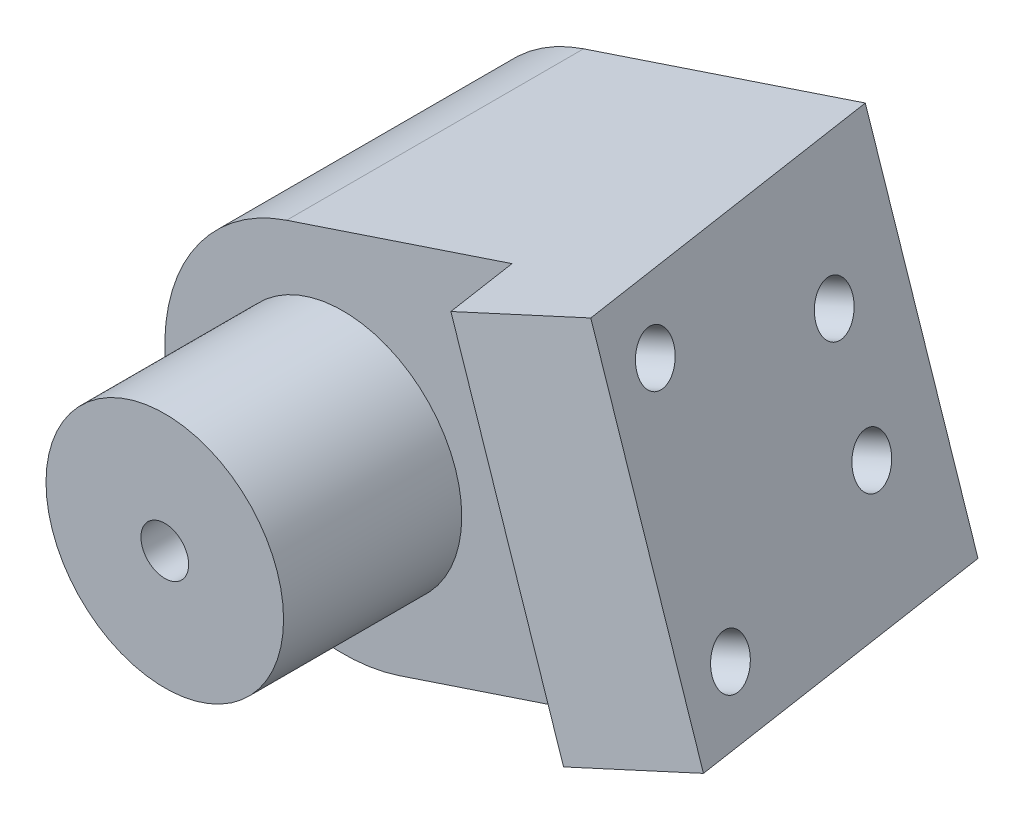
SolidWorks part; units mm, degrees
material "6061 Alloy"
ref_plane "Front Plane" through (0, 0, 0) normal (0, 0, 1) x (1, 0, 0)
ref_plane "Top Plane" through (0, 0, 0) normal (0, 1, 0) x (1, 0, 0)
ref_plane "Right Plane" through (0, 0, 0) normal (1, 0, 0) x (0, 0, -1)
sketch "Sketch1" plane through (0, 0, 0) normal (0, 0, 1) x (1, 0, 0)
  line L0 (0, 0) -> (228.6, 76.2) construction
  line L1 (18.0724, 26.1046) -> (30.1207, -10.0402)
  line L2 (18.0724, 26.1046) -> (-6.0241, 18.0724)
  line L3 (30.1207, -10.0402) -> (6.0241, -18.0724)
  arc A0 (-6.0241, 18.0724) -> (6.0241, -18.0724) centre (0, 0) ccw
  point P6 (24.0966, 8.0322)
  dimension "D1" = 38.1
  dimension "D2" = 76.2
  dimension "D3" = 228.6
  dimension "D4" = 25.4
  dimension "D5" = 38.1
extrude "Boss-Extrude1" add sketch "Sketch1" along normal blind 31.75
sketch "Sketch10" plane through (-6.0241, 18.0724, 0) normal (-0.3162, 0.9487, 0) x (0.9487, 0.3162, 0)
  line L0 (25.4, 0) -> (31.75, 0)
  line L1 (31.75, 0) -> (40.0158, -37.1926)
  line L2 (40.0158, -37.1926) -> (27.2406, -40.0318)
  line L3 (27.2406, -40.0318) -> (25.4, -31.75)
  line L4 (25.4, -31.75) -> (25.4, 0) construction
  line L5 (25.4, 0) -> (25.4, -31.75)
  dimension "D1" = 38.1
  dimension "D2" = 6.35
  dimension "D3" = 12.53
extrude "Boss-Extrude4" add sketch "Sketch10" against normal blind 38.1 contours L1 L2 L3 L5 L0
sketch "Sketch11" plane through (0, 0, 31.75) normal (0, 0, 1) x (1, 0, 0)
  circle A0 centre (0, 0) radius 12.7
  dimension "D1" = 25.4
extrude "Boss-Extrude5" add sketch "Sketch11" along normal blind 19.05
hole_wizard "1/4-20 Tapped Hole3" positions "Sketch13" profile "Sketch12" tap size "1/4-20" standard "ANSI Inch"
sketch "Sketch13" plane through (0, 0, 50.8) normal (0, 0, 1) x (1, 0, 0)
  point P0 (0, 0)
sketch "Sketch12" plane through (0, 0, 50.8) normal (1, 0, 0) x (0, -1, 0)
  line L0 (0, 0) -> (0, 39.6338)
  line L1 (0, 39.6338) -> (2.5527, 38.1)
  line L2 (2.5527, 38.1) -> (2.5527, 0)
  line L5 (2.5527, 0) -> (0, 0)
  line L10 (0, 39.6338) -> (-2.5527, 38.1) construction
  line L11 (0, -6.35) -> (0, 107.95) construction
  dimension "Tap Drill Dia." = 5.1054
  dimension "Tap Drill Depth" = 38.1
  dimension "Drill Angle" = 118
cosmetic thread "Hole Thread9" parameters "D1"=34.925, "D2"=6.35
hole_wizard "1/4-20 Tapped Hole4" positions "Sketch15" profile "Sketch14" tap size "1/4-20" standard "ANSI Inch"
sketch "Sketch15" plane through (28.703, 9.5677, -6.7241) normal (0.9261, 0.3087, -0.217) x (-0.2058, -0.0686, -0.9762)
  line L0 (-44.9882, -19.05) -> (-44.9882, 19.05) construction
  line L1 (-6.8882, 19.05) -> (-44.9882, 19.05) construction
  line L2 (-6.8882, -19.05) -> (-44.9882, -19.05) construction
  line L3 (-6.8882, -19.05) -> (-6.8882, 19.05) construction
  point P0 (-38.6382, 12.7)
  point P2 (-16.4132, 6.35)
  point P4 (-16.4132, -6.35)
  point P6 (-38.6382, -12.7)
  dimension "D1" = 6.35
  dimension "D2" = 6.35
  dimension "D3" = 6.35
  dimension "D4" = 12.7
  dimension "D5" = 12.7
  dimension "D6" = 9.525
sketch "Sketch14" plane through (32.6393, 24.2667, 30.9938) normal (-0.0699, 0.7054, 0.7054) x (-0.3708, 0.6381, -0.6748)
  line L0 (0, 0) -> (0, 14.2338)
  line L1 (0, 14.2338) -> (2.5527, 12.7)
  line L2 (2.5527, 12.7) -> (2.5527, 0)
  line L5 (2.5527, 0) -> (0, 0)
  line L10 (0, 14.2338) -> (-2.5527, 12.7) construction
  line L11 (0, -6.35) -> (0, 107.95) construction
  dimension "Tap Drill Dia." = 5.1054
  dimension "Tap Drill Depth" = 12.7
  dimension "Drill Angle" = 118
cosmetic thread "Hole Thread10" parameters "D1"=11.7093, "D2"=6.35
cosmetic thread "Hole Thread11" parameters "D1"=12.7, "D2"=6.35
cosmetic thread "Hole Thread12" parameters "D1"=12.7, "D2"=6.35
cosmetic thread "Hole Thread13" parameters "D1"=11.7093, "D2"=6.35
sketch "Sketch16" plane through (0, 0, 0) normal (0, 0, -1) x (-1, 0, 0)
  line L0 (0, 0) -> (-27.1086, 9.0362) construction
  line L1 (-30.5782, -6.541) -> (-16.9994, -3.995)
  line L2 (-31.8416, -5.1627) -> (-17.2919, -2.4347)
  line L4 (-22.0885, 24.0966) -> (0, 0) construction
  line L5 (0, 0) -> (-32.1287, -6.0241) construction
  line L6 (-22.3756, 23.2351) -> (-12.3728, 12.3229)
  line L7 (5.0201, 15.0603) -> (-22.0885, 24.0966)
  line L8 (-22.0885, 24.0966) -> (-32.1287, -6.0241)
  line L9 (-32.1287, -6.0241) -> (-5.0201, -15.0603)
  line L10 (-1.8814, 17.3609) -> (-20.538, 23.5797)
  line L11 (-22.3756, 23.2351) -> (-31.8416, -5.1627)
  line L12 (-30.5782, -6.541) -> (-11.9216, -12.7598)
  line L13 (-20.538, 23.5797) -> (-11.2025, 13.3956)
  line L14 (-14.6146, 17.1178) -> (-15.7848, 16.0451) construction
  arc A0 (-16.9994, -3.995) -> (-11.9216, -12.7598) centre (0, 0) ccw
  arc A1 (-12.3728, 12.3229) -> (-17.2919, -2.4347) centre (0, 0) ccw
  arc A3 (-5.0201, -15.0603) -> (5.0201, 15.0603) centre (0, 0) ccw
  arc A5 (-1.8814, 17.3609) -> (-11.2025, 13.3956) centre (0, 0) ccw
  point P14 (-15.1997, 16.5815)
  dimension "D2" = 17.4625
  dimension "D3" = 1.5875
  dimension "D1" = 3.175
extrude "Cut-Extrude3" cut sketch "Sketch16" against normal blind 3.175
sketch "Sketch17" plane through (0, 0, 0) normal (0, 0, -1) x (-1, 0, 0)
  circle A0 centre (0, 0) radius 15.875
  dimension "D1" = 31.75
extrude "Cut-Extrude4" cut sketch "Sketch17" against normal blind 15.875
fillet "Fillet3" radius 1.5875 10 edges at (1.8814, 17.3609, 1.5875) (11.2025, 13.3956, 1.5875) (20.538, 23.5797, 1.5875) (22.3756, 23.2351, 1.5875) (12.3728, 12.3229, 1.5875) (17.2919, -2.4347, 1.5875) (16.9994, -3.995, 1.5875) (11.9216, -12.7598, 1.5875) (31.8416, -5.1627, 1.5875) (30.5782, -6.541, 1.5875)
ref_axis "Axis1" through (0, 0, 15.875) along (0, 0, 1)
sketch "Sketch18" plane through (28.703, 9.5677, -6.7241) normal (0.9261, 0.3087, -0.217) x (-0.2058, -0.0686, -0.9762)
  line L0 (-6.8882, 19.05) -> (-44.9882, -19.05) construction
  line L1 (-44.9882, -19.05) -> (-44.9882, 19.05) construction
  line L2 (-6.8882, -19.05) -> (-44.9882, 19.05) construction
  point P9 (-25.9382, 0)
sketch "Sketch19" plane through (0, 0, 15.875) normal (0, 0, -1) x (-1, 0, 0)
  line L0 (0, 0) -> (0, 15.875) construction
  line L1 (1.5875, 4.4901) -> (1.5875, 15.7954)
  line L2 (-1.5875, 4.4901) -> (-1.5875, 15.7954)
  line L3 (-1.5875, 10.1428) -> (1.5875, 10.1428) construction
  line L4 (3.7798, 2.8973) -> (14.5318, 6.3909)
  line L5 (4.7609, -0.1223) -> (15.5129, 3.3713)
  line L6 (3.9235, -2.6995) -> (10.5686, -11.8457)
  line L7 (1.3549, -4.5657) -> (8, -13.7119)
  line L8 (-1.3549, -4.5657) -> (-8, -13.7119)
  line L9 (-3.9235, -2.6995) -> (-10.5686, -11.8457)
  line L10 (-4.7609, -0.1223) -> (-15.5129, 3.3713)
  line L11 (-3.7798, 2.8973) -> (-14.5318, 6.3909)
  arc A0 (-1.5875, 4.4901) -> (-3.7798, 2.8973) centre (0, 0) ccw
  circle A1 centre (0, 0) radius 15.875 construction
  circle A2 centre (0, 0) radius 15.875 construction
  circle A3 centre (0, 0) radius 3.175 construction
  arc A4 (-4.7609, -0.1223) -> (-3.9235, -2.6995) centre (0, 0) ccw
  arc A5 (3.7798, 2.8973) -> (1.5875, 4.4901) centre (0, 0) ccw
  arc A6 (3.9235, -2.6995) -> (4.7609, -0.1223) centre (0, 0) ccw
  arc A7 (-1.3549, -4.5657) -> (1.3549, -4.5657) centre (0, 0) ccw
  arc A8 (-15.5129, 3.3713) -> (-10.5686, -11.8457) centre (0, 0) ccw
  arc A9 (-1.5875, 15.7954) -> (-14.5318, 6.3909) centre (0, 0) ccw
  arc A10 (14.5318, 6.3909) -> (1.5875, 15.7954) centre (0, 0) ccw
  arc A11 (10.5686, -11.8457) -> (15.5129, 3.3713) centre (0, 0) ccw
  arc A12 (-8, -13.7119) -> (8, -13.7119) centre (0, 0) ccw
  point P14 (0, 10.1428)
  point P34 (0, 0)
  dimension "D2" = 1.5875
  dimension "D3" = 6.35
  dimension "D4" = 5
  dimension "D1" = 3.175
extrude "Cut-Extrude5" cut sketch "Sketch19" against normal blind 6.35
fillet "Fillet4" radius 1.5875 20 edges at (-1.5875, 4.4901, 19.05) (-3.7798, 2.8973, 19.05) (-14.5318, 6.3909, 19.05) (-1.5875, 15.7954, 19.05) (-10.5686, -11.8457, 19.05) (-15.5129, 3.3713, 19.05) (-3.9235, -2.6995, 19.05) (-4.7609, -0.1223, 19.05) (1.3549, -4.5657, 19.05) (-1.3549, -4.5657, 19.05) (-8, -13.7119, 19.05) (8, -13.7119, 19.05) (10.5686, -11.8457, 19.05) (3.9235, -2.6995, 19.05) (4.7609, -0.1223, 19.05) (15.5129, 3.3713, 19.05) (14.5318, 6.3909, 19.05) (1.5875, 15.7954, 19.05) (1.5875, 4.4901, 19.05) (3.7798, 2.8973, 19.05)
